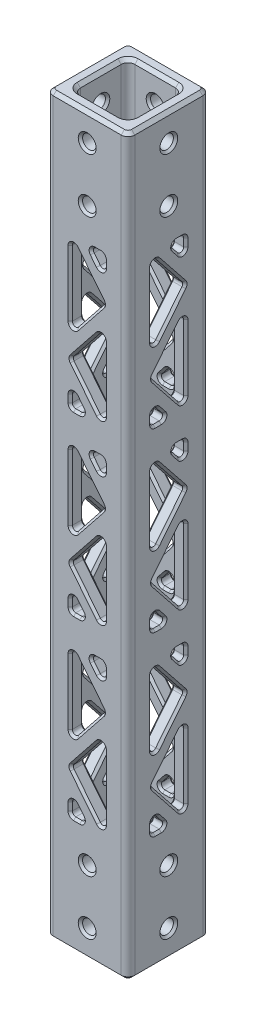
SolidWorks part; units mm, degrees
note: '?' marks a value the reader was unsure of.
ref_plane "Front Plane" through (0, 0, 0) normal (0, 0, 1) x (1, 0, 0)
ref_plane "Top Plane" through (0, 0, 0) normal (0, 1, 0) x (1, 0, 0)
ref_plane "Right Plane" through (0, 0, 0) normal (1, 0, 0) x (0, 0, -1)
sketch "Sketch1" plane through (0, 0, 0) normal (0, 1, 0) x (1, 0, 0)
  line L1 (-9.525, -9.525) -> (9.525, -9.525)
  line L2 (-9.525, -9.525) -> (-9.525, 9.525)
  line L3 (-9.525, 9.525) -> (9.525, 9.525)
  line L4 (9.525, -9.525) -> (9.525, 9.525)
  line L5 (-9.525, -9.525) -> (9.525, 9.525) construction
  line L6 (-9.525, 9.525) -> (9.525, -9.525) construction
  line L7 (-6.35, -6.35) -> (6.35, -6.35)
  line L8 (-6.35, -6.35) -> (-6.35, 6.35)
  line L9 (-6.35, 6.35) -> (6.35, 6.35)
  line L10 (6.35, -6.35) -> (6.35, 6.35)
  line L11 (-6.35, -6.35) -> (6.35, 6.35) construction
  line L12 (-6.35, 6.35) -> (6.35, -6.35) construction
  point P0 (0, 0)
  point P6 (0, 0)
  dimension "D1" = 19.05
  dimension "D2" = 19.05
  dimension "D3" = 12.7
extrude "Boss-Extrude1" add sketch "Sketch1" along normal mid plane 171.45 contours L3 L4 L1 L2
hole_wizard "1/8 (0.125) Diameter Hole1" positions "Sketch8" profile "Sketch9" hole size "1/8" standard "ANSI Inch" end condition through all
sketch "Sketch8" plane through (-9.525, 0, 0) normal (-1, 0, 0) x (0, 0, 1)
  line L4 (-9.525, 85.725) -> (9.525, 85.725) construction
  line L5 (0, 79.375) -> (0, 85.725) construction
  point P0 (0, 79.375)
  point P2 (0, 66.675)
  dimension "D1" = 12.7
  dimension "D2" = 6.35
sketch "Sketch9" plane through (-9.525, 79.375, 0) normal (0, 1, 0) x (0, 0, 1)
  line L0 (0, 0) -> (0, 19.05)
  line L1 (0, 19.05) -> (1.5875, 19.05)
  line L2 (1.5875, 19.05) -> (1.5875, 0)
  line L5 (1.5875, 0) -> (0, 0)
  line L11 (0, -6.35) -> (0, 107.95) construction
  dimension "Thru Hole Dia." = 3.175
  dimension "Thru Hole Depth" = 19.05
hole_wizard "1/8 (0.125) Diameter Hole2" positions "Sketch10" profile "Sketch11" hole size "1/8" standard "ANSI Inch" end condition through all
sketch "Sketch10" plane through (-9.525, 0, 0) normal (-1, 0, 0) x (0, 0, 1)
  line L0 (0, -85.725) -> (0, -79.375) construction
  line L1 (-9.525, -85.725) -> (9.525, -85.725) construction
  point P0 (0, -66.675)
  point P2 (0, -79.375)
  dimension "D1" = 12.7
  dimension "D2" = 6.35
sketch "Sketch11" plane through (-9.525, -66.675, 0) normal (0, 1, 0) x (0, 0, 1)
  line L0 (0, 0) -> (0, 19.05)
  line L1 (0, 19.05) -> (1.5875, 19.05)
  line L2 (1.5875, 19.05) -> (1.5875, 0)
  line L5 (1.5875, 0) -> (0, 0)
  line L11 (0, -6.35) -> (0, 107.95) construction
  dimension "Thru Hole Dia." = 3.175
  dimension "Thru Hole Depth" = 19.05
hole_wizard "1/8 (0.125) Diameter Hole3" positions "Sketch17" profile "Sketch16" hole size "1/8" standard "ANSI Inch" end condition through all
sketch "Sketch17" plane through (0, 0, 9.525) normal (0, 0, 1) x (1, 0, 0)
  line L0 (0, -85.725) -> (0, -79.375) construction
  line L1 (-9.525, -85.725) -> (9.525, -85.725) construction
  line L2 (0, -79.375) -> (0, -66.675) construction
  line L4 (0, 66.675) -> (0, 79.375) construction
  line L5 (0, 79.375) -> (0, 85.725) construction
  line L6 (-9.525, 85.725) -> (9.525, 85.725) construction
  point P0 (0, 79.375)
  point P2 (0, 66.675)
  point P4 (0, -66.675)
  point P6 (0, -79.375)
  dimension "D1" = 6.35
  dimension "D2" = 12.7
sketch "Sketch16" plane through (0, 79.375, 9.525) normal (1, 0, 0) x (0, -1, 0)
  line L0 (0, 0) -> (0, 19.05)
  line L1 (0, 19.05) -> (1.5875, 19.05)
  line L2 (1.5875, 19.05) -> (1.5875, 0)
  line L5 (1.5875, 0) -> (0, 0)
  line L11 (0, -6.35) -> (0, 107.95) construction
  dimension "Thru Hole Dia." = 3.175
  dimension "Thru Hole Depth" = 19.05
sketch "Sketch14" plane through (0, 0, 0) normal (1, 0, 0) x (0, 0, -1)
  line L0 (0, 65.0875) -> (0, 58.7375) construction
  line L3 (-3.9688, 58.7375) -> (3.9688, 58.7375) construction
  line L6 (-3.9688, 58.7375) -> (-3.9688, -58.7375) construction
  line L9 (-3.9688, -58.7375) -> (3.9688, -58.7375) construction
  line L10 (3.9688, -58.7375) -> (3.9688, 58.7375) construction
  line L11 (0, -65.0875) -> (0, -58.7375) construction
  line L12 (-3.9688, 23.8125) -> (3.9688, 23.8125) construction
  line L13 (-3.9688, 17.4625) -> (3.9688, 17.4625) construction
  line L14 (-3.9688, -17.4625) -> (3.9688, -17.4625) construction
  line L15 (-3.9688, -23.8125) -> (3.9688, -23.8125) construction
  line L16 (0, 17.4625) -> (0, 23.8125) construction
  line L17 (0, -23.8125) -> (0, -17.4625) construction
  line L18 (-3.9688, 53.8821) -> (-3.9688, 58.7375)
  line L19 (-3.9688, 58.7375) -> (-0.0935, 58.7375)
  line L20 (-0.0935, 58.7375) -> (-3.9688, 53.8821)
  line L21 (3.9688, 58.7375) -> (-3.9688, 48.7924)
  line L22 (-3.9688, 48.7924) -> (3.9688, 38.8473)
  line L23 (3.9688, 38.8473) -> (3.9688, 58.7375)
  line L24 (0, 53.765) -> (-2.4815, 55.7455) construction
  line L25 (-3.9688, 43.7027) -> (3.9688, 33.7576)
  line L26 (3.9688, 33.7576) -> (-3.9688, 23.8125)
  line L27 (-3.9688, 23.8125) -> (-3.9688, 43.7027)
  line L28 (0, 43.8199) -> (-2.4815, 41.8393) construction
  line L29 (0, -58.7375) -> (0, -23.8125) construction
  line L30 (0, -17.4625) -> (0, 17.4625) construction
  line L31 (0, 23.8125) -> (0, 58.7375) construction
  line L32 (0.0935, 23.8125) -> (3.9688, 23.8125)
  line L33 (3.9688, 23.8125) -> (3.9688, 28.6679)
  line L34 (3.9688, 28.6679) -> (0.0935, 23.8125)
  line L35 (0, 28.785) -> (2.4815, 26.8045) construction
  line L36 (-0.0935, 17.4625) -> (-3.9688, 17.4625)
  line L37 (-3.9688, 17.4625) -> (-3.9688, 12.6071)
  line L38 (-3.9688, 12.6071) -> (-0.0935, 17.4625)
  line L39 (3.9688, 17.4625) -> (-3.9688, 7.5174)
  line L40 (-3.9688, 7.5174) -> (3.9688, -2.4277)
  line L41 (3.9688, -2.4277) -> (3.9688, 17.4625)
  line L42 (0, 12.49) -> (-2.4815, 14.4705) construction
  line L43 (-3.9688, -17.4625) -> (3.9688, -7.5174)
  line L44 (3.9688, -7.5174) -> (-3.9688, 2.4277)
  line L45 (-3.9688, 2.4277) -> (-3.9688, -17.4625)
  line L46 (0, 2.5449) -> (-2.4815, 0.5643) construction
  line L47 (0.0935, -17.4625) -> (3.9688, -17.4625)
  line L48 (3.9688, -17.4625) -> (3.9688, -12.6071)
  line L49 (3.9688, -12.6071) -> (0.0935, -17.4625)
  line L50 (2.4815, -14.4705) -> (0, -12.49) construction
  line L51 (-3.9688, -23.8125) -> (-0.0935, -23.8125)
  line L52 (-0.0935, -23.8125) -> (-3.9688, -28.6679)
  line L53 (-3.9688, -28.6679) -> (-3.9688, -23.8125)
  line L54 (3.9688, -23.8125) -> (-3.9688, -33.7576)
  line L55 (-3.9688, -33.7576) -> (3.9688, -43.7027)
  line L56 (3.9688, -43.7027) -> (3.9688, -23.8125)
  line L57 (-3.9688, -58.7375) -> (3.9688, -48.7924)
  line L58 (3.9688, -48.7924) -> (-3.9688, -38.8473)
  line L59 (-3.9688, -38.8473) -> (-3.9688, -58.7375)
  line L60 (0.0935, -58.7375) -> (3.9688, -58.7375)
  line L61 (3.9688, -58.7375) -> (3.9688, -53.8821)
  line L62 (3.9688, -53.8821) -> (0.0935, -58.7375)
  line L63 (2.0311, -56.3098) -> (-0.4504, -54.3292) construction
  line L65 (0, -28.785) -> (-2.4815, -26.8045) construction
  line L66 (0, -43.8199) -> (2.4815, -41.8393) construction
  circle A8 centre (0, 66.675) radius 1.5875 construction
  circle A9 centre (0, -66.675) radius 1.5875 construction
  dimension "D1" = 6.35
  dimension "D2" = 6.35
  dimension "D3" = 7.9375
  dimension "D4" = 3.175
extrude "Cut-Extrude1" cut sketch "Sketch14" against normal up to next
ref_axis "Axis1" through (0, 94.2975, 0) along (0, -1, 0)?
pattern_circular "CirPattern1" count 4 over 360 about axis through (0, 0, 0) along (0, 1, 0) of "Cut-Extrude1"
fillet "Fillet1" radius 1.5875 8 edges at (9.525, 0, -9.525) (9.525, 0, 9.525) (-9.525, 0, -9.525) (-9.525, 0, 9.525) (6.35, 0, -6.35) (6.35, 0, 6.35) (-6.35, 0, 6.35) (-6.35, 0, -6.35)
fillet "Fillet2" radius 0.7937 72 edges at (-3.9688, -53.8821, 7.9375) (-0.0935, -58.7375, 7.9375) (3.9687, -58.7375, 7.9375) (-3.9688, -48.7924, 7.9375) (-3.9688, -23.8125, 7.9375) (3.9687, -23.8125, 7.9375) (3.9687, -17.4625, 7.9375) (-3.9688, -7.5174, 7.9375) (-3.9688, -2.4277, 7.9375) (-3.9688, 17.4625, 7.9375) (3.9687, 7.5174, 7.9375) (0.0935, 17.4625, 7.9375) (-3.9688, 23.8125, 7.9375) (-0.0935, 23.8125, 7.9375) (3.9687, 23.8125, 7.9375) (3.9687, 43.7027, 7.9375) (-3.9688, 38.8473, 7.9375) (3.9687, 48.7924, 7.9375) (-3.9688, 58.7375, 7.9375) (3.9687, 53.8821, 7.9375) (7.9375, -58.7375, -3.9687) (7.9375, -58.7375, 3.9688) (7.9375, -38.8473, -3.9688) (7.9375, -33.7576, -3.9688) (7.9375, -43.7027, 3.9688) (7.9375, -28.6679, -3.9687) (7.9375, -23.8125, -3.9688) (7.9375, -17.4625, 3.9688) (7.9375, -17.4625, -3.9687) (7.9375, -7.5174, 3.9688) (7.9375, 2.4277, -3.9687) (7.9375, 17.4625, 3.9688) (7.9375, 23.8125, 3.9688) (7.9375, 23.8125, -3.9688) (7.9375, 48.7924, -3.9688) (7.9375, 58.7375, 3.9688) (7.9375, 53.8821, -3.9688) (7.9375, 58.7375, -0.0935) (7.9375, 58.7375, -3.9688) (3.9688, -53.8821, -7.9375) (0.0935, -58.7375, -7.9375) (-3.9687, -38.8473, -7.9375) (-3.9687, -33.7576, -7.9375) (-3.9687, -28.6679, -7.9375) (-0.0935, -23.8125, -7.9375) (0.0935, -17.4625, -7.9375) (-3.9687, -17.4625, -7.9375) (3.9688, -7.5174, -7.9375) (3.9688, -2.4277, -7.9375) (-3.9687, 7.5174, -7.9375) (3.9688, 17.4625, -7.9375) (-3.9687, 17.4625, -7.9375) (-0.0935, 17.4625, -7.9375) (3.9688, 58.7375, -7.9375) (-0.0935, 58.7375, -7.9375) (-3.9687, 58.7375, -7.9375) (-7.9375, -58.7375, -0.0935) (-7.9375, -58.7375, -3.9688) (-7.9375, -38.8473, 3.9688) (-7.9375, -48.7924, -3.9687) (-7.9375, -28.6679, 3.9687) (-7.9375, -23.8125, 0.0935) (-7.9375, -17.4625, -0.0935) (-7.9375, 2.4277, 3.9687) (-7.9375, -2.4277, -3.9687) (-7.9375, 17.4625, -3.9688) (-7.9375, 28.6679, -3.9688) (-7.9375, 23.8125, -0.0935) (-7.9375, 43.7027, 3.9688) (-7.9375, 33.7576, -3.9688) (-7.9375, 38.8473, -3.9688) (-7.9375, 58.7375, 0.0935)
chamfer "Chamfer4" distance 0.762 angle 45 32 edges at (-5.885, -85.725, -5.885) (0, -85.725, -6.35) (5.885, -85.725, -5.885) (6.35, -85.725, 0) (5.885, -85.725, 5.885) (0, -85.725, 6.35) (-5.885, -85.725, 5.885) (-6.35, -85.725, 0) (-9.06, -85.725, -9.06) (-9.525, -85.725, 0) (-9.06, -85.725, 9.06) (0, -85.725, 9.525) (9.06, -85.725, 9.06) (9.525, -85.725, 0) (9.06, -85.725, -9.06) (0, -85.725, -9.525) (5.885, 85.725, -5.885) (0, 85.725, -6.35) (-5.885, 85.725, -5.885) (-6.35, 85.725, 0) (-5.885, 85.725, 5.885) (0, 85.725, 6.35) (5.885, 85.725, 5.885) (6.35, 85.725, 0) (9.06, 85.725, 9.06) (0, 85.725, 9.525) (-9.06, 85.725, 9.06) (-9.525, 85.725, 0) (-9.06, 85.725, -9.06) (0, 85.725, -9.525) (9.06, 85.725, -9.06) (9.525, 85.725, 0)
chamfer "Chamfer3" distance 0.508 angle 45 608 edges at (-3.4373, -15.9447, -6.35) (-3.4373, -15.9447, -9.525) (3.7469, -7.5174, -6.35) (3.7469, -7.5174, -9.525) (-3.4373, 0.9099, -6.35) (-3.4373, 0.9099, -9.525) (3.4373, -0.9099, -6.35) (3.4373, -0.9099, -9.525) (-3.7469, 7.5174, -6.35) (-3.7469, 7.5174, -9.525) (3.4373, 15.9447, -6.35) (3.4373, 15.9447, -9.525) (-3.4373, 14.1249, -6.35) (-3.4373, 14.1249, -9.525) (-3.7363, 17.23, -6.35) (-3.7363, 17.23, -9.525) (-1.0274, 17.013, -6.35) (-1.0274, 17.013, -9.525) (1.0274, 24.262, -6.35) (1.0274, 24.262, -9.525) (3.7363, 24.045, -6.35) (3.7363, 24.045, -9.525) (3.4373, 27.1501, -6.35) (3.4373, 27.1501, -9.525) (-3.4373, 25.3303, -6.35) (-3.4373, 25.3303, -9.525) (-3.4373, 42.1849, -6.35) (-3.4373, 42.1849, -9.525) (3.7469, 33.7576, -6.35) (3.7469, 33.7576, -9.525) (3.4373, 40.3651, -6.35) (3.4373, 40.3651, -9.525) (-3.7469, 48.7924, -6.35) (-3.7469, 48.7924, -9.525) (3.4373, 57.2197, -6.35) (3.4373, 57.2197, -9.525) (-3.4373, 55.3999, -6.35) (-3.4373, 55.3999, -9.525) (-1.0274, 58.288, -6.35) (-1.0274, 58.288, -9.525) (-3.7363, 58.505, -6.35) (-3.7363, 58.505, -9.525) (6.35, -57.2197, -3.4373) (9.525, -57.2197, -3.4373) (6.35, -58.288, 1.0274) (9.525, -58.288, 1.0274) (6.35, -58.505, 3.7363) (9.525, -58.505, 3.7363) (6.35, -55.3999, 3.4373) (9.525, -55.3999, 3.4373) (6.35, -48.7924, 3.7469) (9.525, -48.7924, 3.7469) (6.35, -40.3651, -3.4373) (9.525, -40.3651, -3.4373) (6.35, -33.7576, -3.7469) (9.525, -33.7576, -3.7469) (6.35, -42.1849, 3.4373) (9.525, -42.1849, 3.4373) (6.35, -25.3303, 3.4373) (9.525, -25.3303, 3.4373) (6.35, -27.1501, -3.4373) (9.525, -27.1501, -3.4373) (6.35, -24.045, -3.7363) (9.525, -24.045, -3.7363) (6.35, -24.262, -1.0274) (9.525, -24.262, -1.0274) (6.35, -17.013, 1.0274) (9.525, -17.013, 1.0274) (6.35, -14.1249, 3.4373) (9.525, -14.1249, 3.4373) (6.35, -17.23, 3.7363) (9.525, -17.23, 3.7363) (6.35, -15.9447, -3.4373) (9.525, -15.9447, -3.4373) (6.35, -7.5174, 3.7469) (9.525, -7.5174, 3.7469) (6.35, 0.9099, -3.4373) (9.525, 0.9099, -3.4373) (6.35, -0.9099, 3.4373) (9.525, -0.9099, 3.4373) (6.35, 7.5174, -3.7469) (9.525, 7.5174, -3.7469) (6.35, 15.9447, 3.4373) (9.525, 15.9447, 3.4373) (6.35, 14.1249, -3.4373) (9.525, 14.1249, -3.4373) (6.35, 17.23, -3.7363) (9.525, 17.23, -3.7363) (6.35, 17.013, -1.0274) (9.525, 17.013, -1.0274) (6.35, 27.1501, 3.4373) (9.525, 27.1501, 3.4373) (6.35, 24.045, 3.7363) (9.525, 24.045, 3.7363) (6.35, 24.262, 1.0274) (9.525, 24.262, 1.0274) (6.35, 25.3303, -3.4373) (9.525, 25.3303, -3.4373) (6.35, 33.7576, 3.7469) (9.525, 33.7576, 3.7469) (6.35, 42.1849, -3.4373) (9.525, 42.1849, -3.4373) (6.35, 40.3651, 3.4373) (9.525, 40.3651, 3.4373) (6.35, 48.7924, -3.7469) (9.525, 48.7924, -3.7469) (6.35, 57.2197, 3.4373) (9.525, 57.2197, 3.4373) (6.35, 55.3999, -3.4373) (9.525, 55.3999, -3.4373) (6.35, 58.288, -1.0274) (9.525, 58.288, -1.0274) (6.35, 58.505, -3.7363) (9.525, 58.505, -3.7363) (-3.4373, -55.3999, 6.35) (-3.4373, -55.3999, 9.525) (-1.0274, -58.288, 6.35) (-1.0274, -58.288, 9.525) (-3.7363, -58.505, 6.35) (-3.7363, -58.505, 9.525) (3.4373, -57.2197, 6.35) (3.4373, -57.2197, 9.525) (3.4373, -40.3651, 6.35) (3.4373, -40.3651, 9.525) (-3.7469, -48.7924, 6.35) (-3.7469, -48.7924, 9.525) (-3.4373, -42.1849, 6.35) (-3.4373, -42.1849, 9.525) (3.7469, -33.7576, 6.35) (3.7469, -33.7576, 9.525) (-3.4373, -25.3303, 6.35) (-3.4373, -25.3303, 9.525) (3.4373, -27.1501, 6.35) (3.4373, -27.1501, 9.525) (3.7363, -24.045, 6.35) (3.7363, -24.045, 9.525) (1.0274, -24.262, 6.35) (1.0274, -24.262, 9.525) (-3.7363, -17.23, 6.35) (-3.7363, -17.23, 9.525) (-3.4373, -14.1249, 6.35) (-3.4373, -14.1249, 9.525) (-1.0274, -17.013, 6.35) (-1.0274, -17.013, 9.525) (3.4373, -15.9447, 6.35) (3.4373, -15.9447, 9.525) (3.4373, 0.9099, 6.35) (3.4373, 0.9099, 9.525) (-3.7469, -7.5174, 6.35) (-3.7469, -7.5174, 9.525) (-3.4373, -0.9099, 6.35) (-3.4373, -0.9099, 9.525) (-3.4373, 15.9447, 6.35) (-3.4373, 15.9447, 9.525) (3.7469, 7.5174, 6.35) (3.7469, 7.5174, 9.525) (3.4373, 14.1249, 6.35) (3.4373, 14.1249, 9.525) (1.0274, 17.013, 6.35) (1.0274, 17.013, 9.525) (3.7363, 17.23, 6.35) (3.7363, 17.23, 9.525) (-3.7363, 24.045, 6.35) (-3.7363, 24.045, 9.525) (-3.4373, 27.1501, 6.35) (-3.4373, 27.1501, 9.525) (-1.0274, 24.262, 6.35) (-1.0274, 24.262, 9.525) (3.4373, 25.3303, 6.35) (3.4373, 25.3303, 9.525) (3.4373, 42.1849, 6.35) (3.4373, 42.1849, 9.525) (-3.7469, 33.7576, 6.35) (-3.7469, 33.7576, 9.525) (-3.4373, 40.3651, 6.35) (-3.4373, 40.3651, 9.525) (3.7469, 48.7924, 6.35) (3.7469, 48.7924, 9.525) (-3.4373, 57.2197, 6.35) (-3.4373, 57.2197, 9.525) (3.4373, 55.3999, 6.35) (3.4373, 55.3999, 9.525) (1.0274, 58.288, 6.35) (1.0274, 58.288, 9.525) (3.7363, 58.505, 6.35) (3.7363, 58.505, 9.525) (6.35, 66.675, 1.5875) (-6.35, 66.675, -1.5875) (-9.525, 66.675, 1.5875) (9.525, 66.675, 1.5875) (-6.35, 79.375, -1.5875) (6.35, 79.375, 1.5875) (9.525, 79.375, 1.5875) (-9.525, 79.375, 1.5875) (-6.35, -79.375, -1.5875) (6.35, -79.375, 1.5875) (9.525, -79.375, 1.5875) (-9.525, -79.375, 1.5875) (6.35, -66.675, 1.5875) (-6.35, -66.675, -1.5875) (-9.525, -66.675, 1.5875) (9.525, -66.675, 1.5875) (-9.525, -58.7375, -2.4588) (-6.35, -58.7375, -2.4588) (-9.525, -56.5513, -1.8384) (-6.35, -56.5513, -1.8384) (-9.525, -57.0464, -3.9688) (-6.35, -57.0464, -3.9688) (-9.525, -53.1266, -0.5095) (-6.35, -53.1266, -0.5095) (-9.525, -48.7924, 3.9688) (-6.35, -48.7924, 3.9688) (-9.525, -44.4582, -0.5095) (-6.35, -44.4582, -0.5095) (-9.525, -33.7576, -3.9688) (-6.35, -33.7576, -3.9688) (-9.525, -38.0918, 0.5095) (-6.35, -38.0918, 0.5095) (-9.525, -29.4234, 0.5095) (-6.35, -29.4234, 0.5095) (-9.525, -25.9987, 1.8384) (-6.35, -25.9987, 1.8384) (-9.525, -25.5036, 3.9688) (-6.35, -25.5036, 3.9688) (-9.525, -23.8125, 2.4588) (-6.35, -23.8125, 2.4588) (-9.525, -15.2763, -1.8384) (-6.35, -15.2763, -1.8384) (-9.525, -15.7714, -3.9688) (-6.35, -15.7714, -3.9688) (-9.525, -17.4625, -2.4588) (-6.35, -17.4625, -2.4588) (-9.525, -11.8516, -0.5095) (-6.35, -11.8516, -0.5095) (-9.525, -7.5174, 3.9688) (-6.35, -7.5174, 3.9688) (-9.525, -3.1832, -0.5095) (-6.35, -3.1832, -0.5095) (-9.525, 7.5174, -3.9688) (-6.35, 7.5174, -3.9688) (-9.525, 3.1832, 0.5095) (-6.35, 3.1832, 0.5095) (-9.525, 11.8516, 0.5095) (-6.35, 11.8516, 0.5095) (-9.525, 15.2763, 1.8384) (-6.35, 15.2763, 1.8384) (-9.525, 15.7714, 3.9688) (-6.35, 15.7714, 3.9688) (-9.525, 17.4625, 2.4588) (-6.35, 17.4625, 2.4588) (-9.525, 25.9987, -1.8384) (-6.35, 25.9987, -1.8384) (-9.525, 25.5036, -3.9688) (-6.35, 25.5036, -3.9688) (-9.525, 23.8125, -2.4588) (-6.35, 23.8125, -2.4588) (-9.525, 29.4234, -0.5095) (-6.35, 29.4234, -0.5095) (-9.525, 33.7576, 3.9688) (-6.35, 33.7576, 3.9688) (-9.525, 38.0918, -0.5095) (-6.35, 38.0918, -0.5095) (-9.525, 48.7924, -3.9688) (-6.35, 48.7924, -3.9688) (1.5875, -79.375, -6.35) (-9.525, 44.4582, 0.5095) (-1.5875, -79.375, 6.35) (-6.35, 44.4582, 0.5095) (1.5875, -79.375, 9.525) (1.5875, -79.375, -9.525) (-9.525, 53.1266, 0.5095) (-6.35, 53.1266, 0.5095) (-9.525, 56.5513, 1.8384) (-6.35, 56.5513, 1.8384) (-9.525, 57.0464, 3.9688) (-6.35, 57.0464, 3.9688) (-9.525, 58.7375, 2.4588) (-6.35, 58.7375, 2.4588) (1.8384, -56.5513, -9.525) (1.8384, -56.5513, -6.35) (3.9688, -57.0464, -9.525) (3.9688, -57.0464, -6.35) (2.4588, -58.7375, -9.525) (2.4588, -58.7375, -6.35) (0.5095, -53.1266, -9.525) (0.5095, -53.1266, -6.35) (-3.9687, -48.7924, -9.525) (-3.9687, -48.7924, -6.35) (0.5095, -44.4582, -9.525) (0.5095, -44.4582, -6.35) (3.9688, -33.7576, -9.525) (3.9688, -33.7576, -6.35) (-0.5095, -38.0918, -9.525) (-0.5095, -38.0918, -6.35) (-0.5095, -29.4234, -9.525) (-0.5095, -29.4234, -6.35) (-3.9687, -25.5036, -9.525) (-3.9687, -25.5036, -6.35) (-2.4588, -23.8125, -9.525) (-2.4588, -23.8125, -6.35) (-1.8384, -25.9987, -9.525) (-1.8384, -25.9987, -6.35) (2.4588, -17.4625, -9.525) (2.4588, -17.4625, -6.35) (1.8384, -15.2763, -9.525) (1.8384, -15.2763, -6.35) (3.9688, -15.7714, -9.525) (3.9688, -15.7714, -6.35) (0.5095, -11.8516, -9.525) (0.5095, -11.8516, -6.35) (-3.9687, -7.5174, -9.525) (-3.9687, -7.5174, -6.35) (0.5095, -3.1832, -9.525) (0.5095, -3.1832, -6.35) (3.9688, 7.5174, -9.525) (3.9688, 7.5174, -6.35) (-0.5095, 3.1832, -9.525) (-0.5095, 3.1832, -6.35) (-0.5095, 11.8516, -9.525) (-0.5095, 11.8516, -6.35) (-1.8384, 15.2763, -9.525) (-1.8384, 15.2763, -6.35) (-3.9687, 15.7714, -9.525) (-3.9687, 15.7714, -6.35) (-2.4588, 17.4625, -9.525) (-2.4588, 17.4625, -6.35) (2.4588, 23.8125, -9.525) (2.4588, 23.8125, -6.35) (1.8384, 25.9987, -9.525) (1.8384, 25.9987, -6.35) (3.9688, 25.5036, -9.525) (3.9688, 25.5036, -6.35) (0.5095, 29.4234, -9.525) (0.5095, 29.4234, -6.35) (-3.9687, 33.7576, -9.525) (-3.9687, 33.7576, -6.35) (0.5095, 38.0918, -9.525) (0.5095, 38.0918, -6.35) (3.9688, 48.7924, -9.525) (3.9688, 48.7924, -6.35) (-0.5095, 44.4582, -9.525) (-0.5095, 44.4582, -6.35) (-0.5095, 53.1266, -9.525) (-0.5095, 53.1266, -6.35) (-1.8384, 56.5513, -9.525) (-1.8384, 56.5513, -6.35) (-3.9687, 57.0464, -9.525) (-1.5875, -66.675, 6.35) (-3.9687, 57.0464, -6.35) (1.5875, -66.675, -6.35) (-2.4588, 58.7375, -9.525) (1.5875, -66.675, -9.525) (-2.4588, 58.7375, -6.35) (1.5875, -66.675, 9.525) (9.525, -53.1266, 0.5095) (6.35, -53.1266, 0.5095) (9.525, -48.7924, -3.9688) (6.35, -48.7924, -3.9688) (9.525, -58.7375, 2.4588) (6.35, -58.7375, 2.4588) (9.525, -56.5513, 1.8384) (6.35, -56.5513, 1.8384) (9.525, -57.0464, 3.9688) (6.35, -57.0464, 3.9688) (9.525, -44.4582, 0.5095) (6.35, -44.4582, 0.5095) (9.525, -38.0918, -0.5095) (6.35, -38.0918, -0.5095) (9.525, -29.4234, -0.5095) (6.35, -29.4234, -0.5095) (9.525, -33.7576, 3.9688) (6.35, -33.7576, 3.9688) (9.525, -25.9987, -1.8384) (6.35, -25.9987, -1.8384) (9.525, -25.5036, -3.9688) (6.35, -25.5036, -3.9688) (9.525, -23.8125, -2.4588) (6.35, -23.8125, -2.4588) (9.525, -17.4625, 2.4588) (6.35, -17.4625, 2.4588) (9.525, -15.2763, 1.8384) (6.35, -15.2763, 1.8384) (9.525, -15.7714, 3.9688) (6.35, -15.7714, 3.9688) (9.525, -11.8516, 0.5095) (6.35, -11.8516, 0.5095) (9.525, -7.5174, -3.9688) (6.35, -7.5174, -3.9688) (9.525, -3.1832, 0.5095) (6.35, -3.1832, 0.5095) (9.525, 7.5174, 3.9688) (6.35, 7.5174, 3.9688) (9.525, 3.1832, -0.5095) (6.35, 3.1832, -0.5095) (9.525, 11.8516, -0.5095) (6.35, 11.8516, -0.5095) (9.525, 15.2763, -1.8384) (6.35, 15.2763, -1.8384) (9.525, 15.7714, -3.9688) (6.35, 15.7714, -3.9688) (9.525, 17.4625, -2.4588) (6.35, 17.4625, -2.4588) (9.525, 25.9987, 1.8384) (6.35, 25.9987, 1.8384) (9.525, 25.5036, 3.9688) (6.35, 25.5036, 3.9688) (9.525, 23.8125, 2.4588) (6.35, 23.8125, 2.4588) (9.525, 29.4234, 0.5095) (6.35, 29.4234, 0.5095) (9.525, 33.7576, -3.9688) (6.35, 33.7576, -3.9688) (9.525, 38.0918, 0.5095) (6.35, 38.0918, 0.5095) (9.525, 48.7924, 3.9688) (6.35, 48.7924, 3.9688) (9.525, 44.4582, -0.5095) (6.35, 44.4582, -0.5095) (9.525, 53.1266, -0.5095) (6.35, 53.1266, -0.5095) (9.525, 56.5513, -1.8384) (6.35, 56.5513, -1.8384) (9.525, 57.0464, -3.9688) (6.35, 57.0464, -3.9688) (9.525, 58.7375, -2.4588) (6.35, 58.7375, -2.4588) (-1.8384, -56.5513, 9.525) (-1.8384, -56.5513, 6.35) (1.5875, 66.675, -6.35) (-3.9688, -57.0464, 9.525) (-1.5875, 66.675, 6.35) (-3.9688, -57.0464, 6.35) (1.5875, 66.675, 9.525) (-2.4588, -58.7375, 9.525) (1.5875, 66.675, -9.525) (-2.4588, -58.7375, 6.35) (-0.5095, -53.1266, 9.525) (-0.5095, -53.1266, 6.35) (3.9687, -48.7924, 9.525) (3.9687, -48.7924, 6.35) (-0.5095, -44.4582, 9.525) (-0.5095, -44.4582, 6.35) (-3.9688, -33.7576, 9.525) (-3.9688, -33.7576, 6.35) (0.5095, -38.0918, 9.525) (0.5095, -38.0918, 6.35) (0.5095, -29.4234, 9.525) (0.5095, -29.4234, 6.35) (1.8384, -25.9987, 9.525) (1.8384, -25.9987, 6.35) (3.9687, -25.5036, 9.525) (3.9687, -25.5036, 6.35) (2.4588, -23.8125, 9.525) (2.4588, -23.8125, 6.35) (-3.9688, -15.7714, 9.525) (-3.9688, -15.7714, 6.35) (-2.4588, -17.4625, 9.525) (-2.4588, -17.4625, 6.35) (-1.8384, -15.2763, 9.525) (-1.8384, -15.2763, 6.35) (-0.5095, -11.8516, 9.525) (-0.5095, -11.8516, 6.35) (3.9687, -7.5174, 9.525) (3.9687, -7.5174, 6.35) (-0.5095, -3.1832, 9.525) (-0.5095, -3.1832, 6.35) (-3.9688, 7.5174, 9.525) (-3.9688, 7.5174, 6.35) (0.5095, 3.1832, 9.525) (0.5095, 3.1832, 6.35) (0.5095, 11.8516, 9.525) (0.5095, 11.8516, 6.35) (1.8384, 15.2763, 9.525) (1.8384, 15.2763, 6.35) (3.9687, 15.7714, 9.525) (3.9687, 15.7714, 6.35) (2.4588, 17.4625, 9.525) (2.4588, 17.4625, 6.35) (-3.9688, 25.5036, 9.525) (-3.9688, 25.5036, 6.35) (-2.4588, 23.8125, 9.525) (-2.4588, 23.8125, 6.35) (-1.8384, 25.9987, 9.525) (-1.8384, 25.9987, 6.35) (-0.5095, 29.4234, 9.525) (-0.5095, 29.4234, 6.35) (3.9687, 33.7576, 9.525) (3.9687, 33.7576, 6.35) (-0.5095, 38.0918, 9.525) (-0.5095, 38.0918, 6.35) (-3.9688, 48.7924, 9.525) (-3.9688, 48.7924, 6.35) (0.5095, 44.4582, 9.525) (0.5095, 44.4582, 6.35) (0.5095, 53.1266, 9.525) (0.5095, 53.1266, 6.35) (1.8384, 56.5513, 9.525) (1.8384, 56.5513, 6.35) (3.9687, 57.0464, 9.525) (3.9687, 57.0464, 6.35) (2.4588, 58.7375, 9.525) (2.4588, 58.7375, 6.35) (-6.35, -58.288, -1.0274) (-9.525, -58.288, -1.0274) (-6.35, -55.3999, -3.4373) (-9.525, -55.3999, -3.4373) (-6.35, -58.505, -3.7363) (-9.525, -58.505, -3.7363) (-6.35, -57.2197, 3.4373) (-9.525, -57.2197, 3.4373) (-6.35, -40.3651, 3.4373) (-9.525, -40.3651, 3.4373) (-6.35, -48.7924, -3.7469) (-9.525, -48.7924, -3.7469) (-6.35, -42.1849, -3.4373) (-9.525, -42.1849, -3.4373) (-6.35, -33.7576, 3.7469) (-9.525, -33.7576, 3.7469) (-6.35, -25.3303, -3.4373) (-9.525, -25.3303, -3.4373) (-6.35, -27.1501, 3.4373) (-9.525, -27.1501, 3.4373) (-6.35, -24.045, 3.7363) (-9.525, -24.045, 3.7363) (-6.35, -24.262, 1.0274) (-9.525, -24.262, 1.0274) (-1.5875, 79.375, 6.35) (-6.35, -14.1249, -3.4373) (-9.525, -14.1249, -3.4373) (-6.35, -17.23, -3.7363) (1.5875, 79.375, -6.35) (-9.525, -17.23, -3.7363) (-6.35, -17.013, -1.0274) (1.5875, 79.375, -9.525) (-9.525, -17.013, -1.0274) (-6.35, -15.9447, 3.4373) (-9.525, -15.9447, 3.4373) (1.5875, 79.375, 9.525) (-6.35, -7.5174, -3.7469) (-9.525, -7.5174, -3.7469) (-6.35, 0.9099, 3.4373) (-9.525, 0.9099, 3.4373) (-6.35, -0.9099, -3.4373) (-9.525, -0.9099, -3.4373) (-6.35, 7.5174, 3.7469) (-9.525, 7.5174, 3.7469) (-6.35, 15.9447, -3.4373) (-9.525, 15.9447, -3.4373) (-6.35, 14.1249, 3.4373) (-9.525, 14.1249, 3.4373) (-6.35, 17.23, 3.7363) (-9.525, 17.23, 3.7363) (-6.35, 17.013, 1.0274) (-9.525, 17.013, 1.0274) (-6.35, 27.1501, -3.4373) (-9.525, 27.1501, -3.4373) (-6.35, 24.045, -3.7363) (-9.525, 24.045, -3.7363) (-6.35, 24.262, -1.0274) (-9.525, 24.262, -1.0274) (-6.35, 25.3303, 3.4373) (-9.525, 25.3303, 3.4373) (-6.35, 42.1849, 3.4373) (-9.525, 42.1849, 3.4373) (-6.35, 33.7576, -3.7469) (-9.525, 33.7576, -3.7469) (-6.35, 40.3651, -3.4373) (-9.525, 40.3651, -3.4373) (-6.35, 48.7924, 3.7469) (-9.525, 48.7924, 3.7469) (-6.35, 57.2197, -3.4373) (-9.525, 57.2197, -3.4373) (-6.35, 55.3999, 3.4373) (-9.525, 55.3999, 3.4373) (-6.35, 58.288, 1.0274) (-9.525, 58.288, 1.0274) (-6.35, 58.505, 3.7363) (-9.525, 58.505, 3.7363) (3.4373, -55.3999, -6.35) (3.4373, -55.3999, -9.525) (3.7363, -58.505, -6.35) (3.7363, -58.505, -9.525) (1.0274, -58.288, -6.35) (1.0274, -58.288, -9.525) (-3.4373, -57.2197, -6.35) (-3.4373, -57.2197, -9.525) (-3.4373, -40.3651, -6.35) (-3.4373, -40.3651, -9.525) (3.7469, -48.7924, -6.35) (3.7469, -48.7924, -9.525) (3.4373, -42.1849, -6.35) (3.4373, -42.1849, -9.525) (-3.7469, -33.7576, -6.35) (-3.7469, -33.7576, -9.525) (-3.7363, -24.045, -6.35) (-3.7363, -24.045, -9.525) (-3.4373, -27.1501, -6.35) (-3.4373, -27.1501, -9.525) (-1.0274, -24.262, -6.35) (-1.0274, -24.262, -9.525) (3.4373, -25.3303, -6.35) (3.4373, -25.3303, -9.525) (1.0274, -17.013, -6.35) (1.0274, -17.013, -9.525) (3.4373, -14.1249, -6.35) (3.4373, -14.1249, -9.525) (3.7363, -17.23, -6.35) (3.7363, -17.23, -9.525)
equation "\"D2@Sketch1\"=\"D1@Sketch1\""
